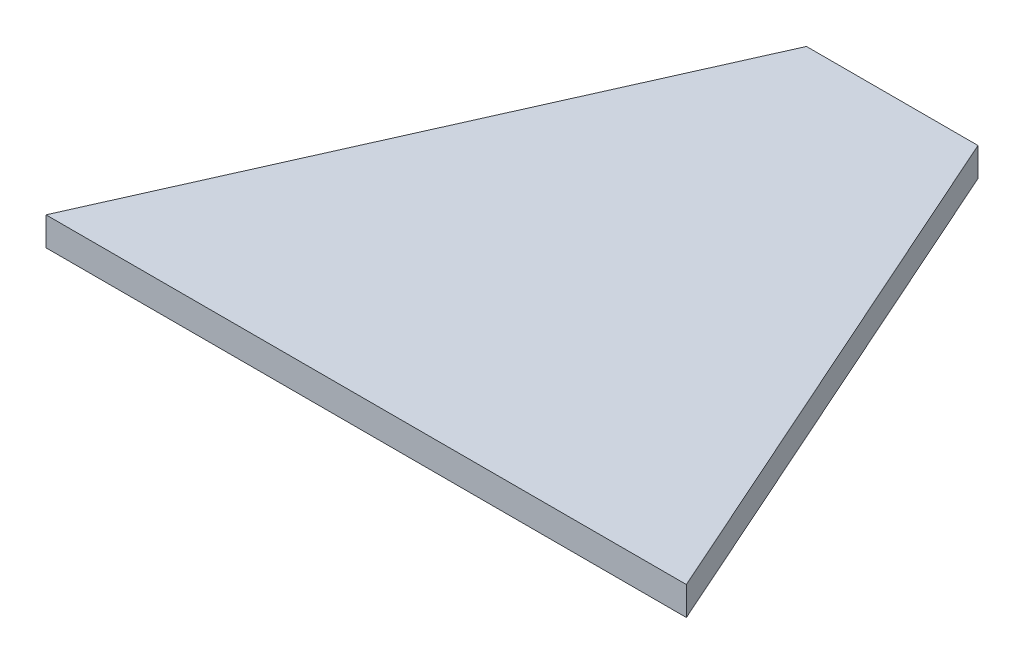
SolidWorks part; units mm, degrees
material "AISI 1020"
ref_plane "Спереди" through (0, 0, 0) normal (0, 0, 1) x (1, 0, 0)
ref_plane "Сверху" through (0, 0, 0) normal (0, 1, 0) x (1, 0, 0)
ref_plane "Справа" through (0, 0, 0) normal (1, 0, 0) x (0, 0, -1)
sketch "Эскиз1" plane through (0, 0, 0) normal (0, 1, 0) x (1, 0, 0)
  line L0 (0, -1000) -> (0, 49000) construction
  line L2 (56, 0) -> (-56, 0)
  line L3 (-56, 0) -> (-15, 92)
  line L4 (-15, 0) -> (-15, 654) construction
  line L5 (-15, 92) -> (15, 92)
  line L6 (-712.5668, 92) -> (-729.0668, 92) construction
  line L7 (-56, -12) -> (-56, -6) construction
  line L8 (56, 0) -> (15, 92)
  point P14 (0, 92)
  point P15 (0, 0)
base flange "Базовая кромка1" sketch "Эскиз1" thickness 5 reverse thickness direction yes parameters "D1"=0.75
sketch "Сгиб-Линии1" [suppressed] plane through (0, 0, 0) normal (0, 1, 0) x (1, 0, 0)
sketch "Граничная рамка1" [suppressed] plane through (0, 0, 0) normal (0, 1, 0) x (1, 0, 0)
sheet metal parameters "Листовой металл3" thickness 5 parameters "D1"=0.75
flat pattern "Развертка3" [suppressed]
sketch "Сгиб-Линии2" plane through (0, 0, 0) normal (0, 1, 0) x (1, 0, 0)
sketch3d "Граничная рамка2" [suppressed]
  line L0 (-56, 92, 0) -> (56, 92, 0) construction
  line L1 (-56, 0, 0) -> (56, 0, 0) construction
  line L2 (-56, 92, 0) -> (-56, 0, 0) construction
  line L3 (56, 92, 0) -> (56, 0, 0) construction
